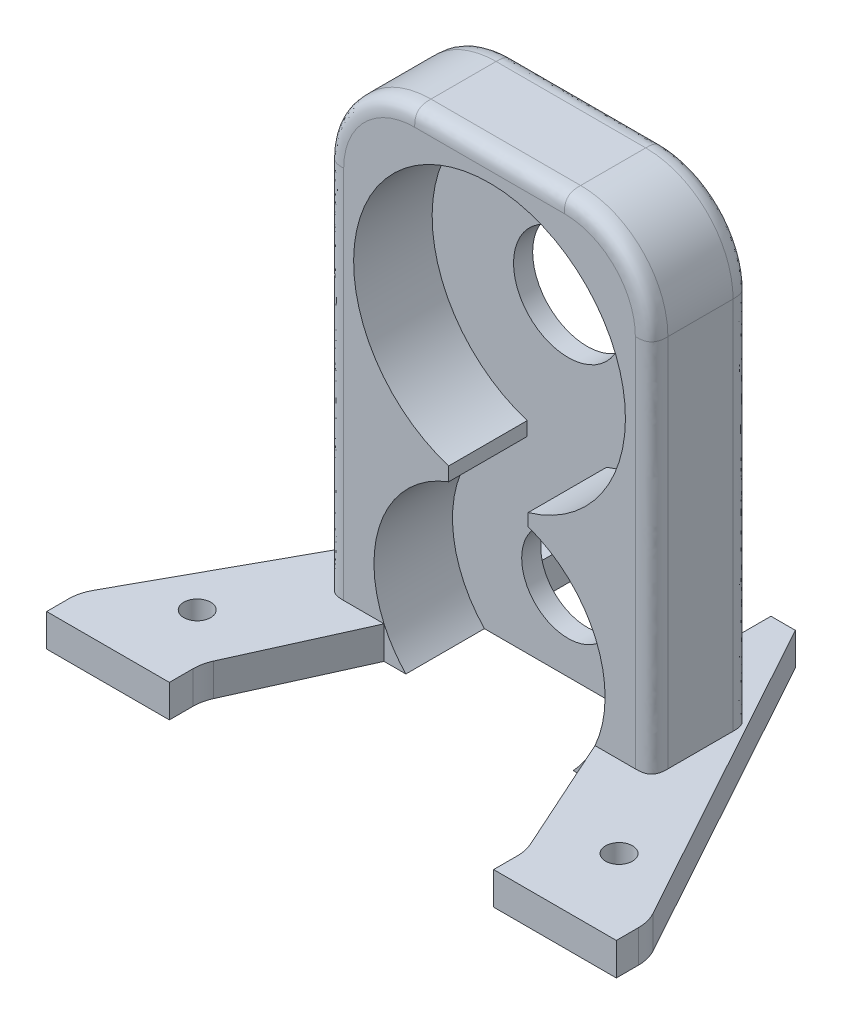
SolidWorks part; units mm, degrees
ref_plane "Plano frontal" through (0, 0, 0) normal (0, 0, 1) x (1, 0, 0)
ref_plane "Plano superior" through (0, 0, 0) normal (0, 1, 0) x (1, 0, 0)
ref_plane "Plano direito" through (0, 0, 0) normal (1, 0, 0) x (0, 0, -1)
sketch "Esboço1" plane through (0, 0, 0) normal (0, 0, 1) x (1, 0, 0)
  line L0 (-19.9192, 0) -> (-10.2762, 0)
  line L1 (-15.1192, 10) -> (-15.1192, 10.8)
  line L2 (15.1192, 9.8) -> (15.1192, 10)
  line L3 (15.1192, 10) -> (19.9192, 10)
  line L10 (0, 9.4378) -> (0, -16.7527) construction
  line L13 (-15.1192, 10) -> (-19.9192, 10)
  line L17 (10.2762, 0) -> (19.9192, 0)
  line L18 (-15.1192, 10) -> (-19.9192, 10)
  line L19 (-19.9192, 10) -> (-19.9192, 50)
  line L20 (0, 0) -> (0, 24) construction
  line L21 (19.9192, 10) -> (19.9192, 50)
  line L22 (-9.1953, 60.7238) -> (9.1953, 60.7238)
  line L23 (0, 26) -> (0, 71.8708) construction
  line L25 (-22.6175, 24) -> (-5.0193, 24) construction
  line L26 (-5.0193, 23.0833) -> (-5.0193, 24.7721)
  line L28 (4.7401, 24.6868) -> (4.7401, 23.1855)
  line L29 (4.7401, 24) -> (24.867, 24) construction
  line L30 (-19.9192, 10) -> (-19.9192, 0)
  line L31 (19.9192, 10) -> (19.9192, 0)
  arc A4 (10.2762, 0) -> (4.7401, 23.1855) centre (0, 9.8) ccw
  arc A5 (4.7401, 24.6868) -> (-5.0193, 24.7721) centre (0, 40.7) ccw
  arc A6 (-19.9192, 50) -> (-9.1953, 60.7238) centre (-9.1953, 50) cw
  arc A7 (19.9192, 50) -> (9.1953, 60.7238) centre (9.1953, 50) ccw
  arc A8 (-5.0193, 23.0833) -> (-10.2762, 0) centre (0, 9.8) ccw
  point P7 (0, 0)
  dimension "D1" = 14.2
  dimension "D2" = 39.8383
  dimension "D4" = 90
  dimension "D5" = 40
  dimension "D9" = 9.8
extrude "Ressalto-extrusão4" add sketch "Esboço1" along normal blind 12 contours A8 L26 A5 L28 A4 L17 L3 L21 A7 L22 A6 L19 L13 L0 region at (-19.1929, 5, 0)
sketch "Esboço2" plane through (0, 0, 0) normal (0, 0, -1) x (-1, 0, 0)
  line L3 (-10.2762, 0) -> (10.2762, 0)
  line L4 (-4.7401, 24.6868) -> (-4.7401, 23.1855)
  line L5 (5.0193, 24.7721) -> (5.0193, 23.0833)
  circle A1 centre (0, 9.8) radius 5.7
  arc A4 (5.0193, 24.7721) -> (-4.7401, 24.6868) centre (0, 40.7) ccw
  arc A5 (10.2762, 0) -> (5.0193, 23.0833) centre (0, 9.8) ccw
  arc A6 (-4.7401, 23.1855) -> (-10.2762, 0) centre (0, 9.8) ccw
  circle A7 centre (0, 40.7) radius 6.7
  dimension "D1" = 11.4
extrude "Ressalto-extrusão5" add sketch "Esboço2" against normal blind 2.35
sketch "Esboço4" plane through (0, 0, 0) normal (0, -1, 0) x (1, 0, 0)
  line L0 (0, -35.3866) -> (0, 38.0559) construction
  line L5 (-19.9192, 31.4197) -> (-19.9192, 27.4197)
  line L8 (-19.9192, 27.4197) -> (-12.9615, 12)
  line L9 (-19.9192, 12) -> (-10.2762, 12) construction
  line L12 (-35, 31.4197) -> (-35, 27.4197)
  line L15 (-35, 27.4197) -> (-13, -12.5803)
  line L17 (-12.9615, 12) -> (-12.9615, 0)
  line L21 (-19.9192, 0) -> (19.9192, 0) construction
  line L22 (-35, 31.4197) -> (-19.9192, 31.4197)
  line L26 (-19.9192, 12) -> (-19.9192, 0) construction
  line L27 (-12.9615, 0) -> (-10, 0)
  line L28 (-10, 0) -> (-10, -12.5803)
  line L29 (-10, -12.5803) -> (-13, -12.5803)
  line L34 (10, -12.5803) -> (13, -12.5803)
  line L35 (10, 0) -> (10, -12.5803)
  line L36 (12.9615, 0) -> (10, 0)
  line L37 (12.9615, 12) -> (12.9615, 0)
  line L38 (19.9192, 27.4197) -> (12.9615, 12)
  line L39 (19.9192, 31.4197) -> (19.9192, 27.4197)
  line L40 (35, 31.4197) -> (19.9192, 31.4197)
  line L41 (35, 31.4197) -> (35, 27.4197)
  line L42 (35, 27.4197) -> (13, -12.5803)
  point P13 (0, -33.5056)
  point P15 (0, 24.5803)
  dimension "D1" = 44
  dimension "D2" = 15.0808
  dimension "D3" = 13
  dimension "D4" = 35
  dimension "D6" = 4
  dimension "D8" = 6.9577
  dimension "D9" = 3
extrude "Ressalto-extrusão7" add sketch "Esboço4" against normal blind 4
sketch "Esboço5" plane through (0, 4, 0) normal (0, 1, 0) x (1, 0, 0)
  line L0 (0, 0) -> (0, 14.0884) construction
  line L3 (-10, 0) -> (-19.9192, 0) construction
  line L4 (-19.9192, -27.4197) -> (-19.9192, -31.4197) construction
  line L5 (-19.9192, 0) -> (-13, 12.5803) construction
  circle A0 centre (-13, 3) radius 1.65
  circle A1 centre (-25.9192, -22) radius 1.65
  circle A2 centre (13, 3) radius 1.65
  circle A3 centre (25.9192, -22) radius 1.65
  dimension "D1" = 3.3
  dimension "D2" = 3.3
  dimension "D3" = 6
  dimension "D4" = 4.6169
  dimension "D5" = 3
  dimension "D6" = 22
extrude "Corte-extrusão1" cut sketch "Esboço5" against normal through all
fillet "Filete1" radius 2 10 edges at (-19.9192, 27, 0) (-16.7782, 57.5829, 0) (19.9192, 27, 0) (16.7782, 57.5829, 0) (-19.9192, 27, 12) (-16.7782, 57.5829, 12) (19.9192, 27, 12) (16.7782, 57.5829, 12) (0, 60.7238, 0) (0, 60.7238, 12) curvature continuous yes
fillet "Filete2" radius 5 4 edges at (-19.9192, 2, 27.4197) (19.9192, 2, 27.4197) (35, 2, 27.4197) (-35, 2, 27.4197)
